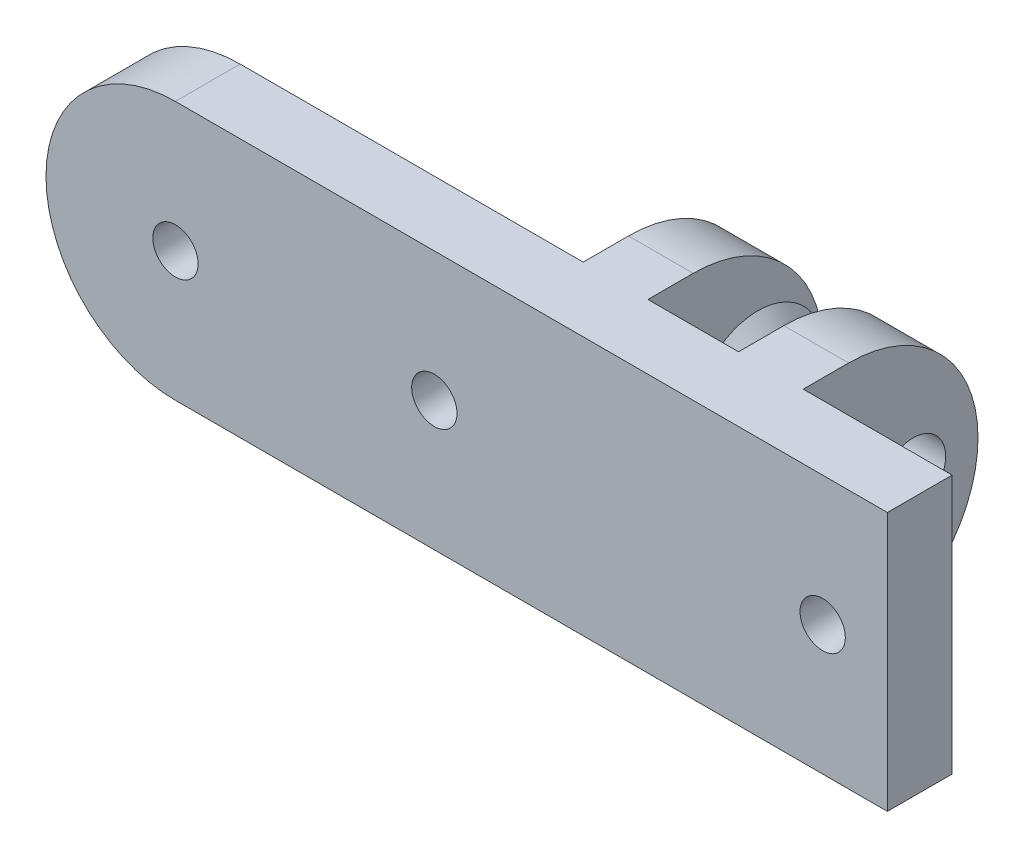
SolidWorks part; units mm, degrees
ref_plane "Спереди" through (0, 0, 0) normal (0, 0, 1) x (1, 0, 0)
ref_plane "Сверху" through (0, 0, 0) normal (0, 1, 0) x (1, 0, 0)
ref_plane "Справа" through (0, 0, 0) normal (1, 0, 0) x (0, 0, -1)
sketch "Эскиз1" plane through (0, 0, 0) normal (0, 0, 1) x (1, 0, 0)
  line L1 (-20, -10) -> (20, -10)
  line L2 (-20, -10) -> (-20, 10)
  line L3 (-20, 10) -> (20, 10)
  line L4 (20, -10) -> (20, 10)
  line L5 (-20, -10) -> (20, 10) construction
  line L6 (-20, 10) -> (20, -10) construction
  line L7 (-3.5, -10) -> (3.5, -10)
  line L8 (-3.5, -10) -> (-3.5, 10)
  line L9 (-3.5, 10) -> (3.5, 10)
  line L10 (3.5, -10) -> (3.5, 10)
  line L11 (-3.5, -10) -> (3.5, 10) construction
  line L12 (-3.5, 10) -> (3.5, -10) construction
  line L13 (-20, 10) -> (-45, 10)
  line L14 (-20, 10) -> (-20, -10)
  line L15 (-20, -10) -> (-45, -10)
  line L16 (-45, 10) -> (-45, -10)
  circle A0 centre (-15, 0) radius 1.75 construction
  circle A1 centre (15, 0) radius 1.75 construction
  circle A2 centre (-15, 0) radius 1.75
  circle A3 centre (15, 0) radius 1.75
  point P0 (0, 0)
  point P12 (0, 0)
  dimension "D1" = 40
  dimension "D2" = 20
  dimension "D3" = 7
  dimension "D4" = 25
extrude "Бобышка-Вытянуть1" add sketch "Эскиз1" along normal blind 5 contours L1 L8 L3 L2 A2 | L10 L1 L4 L3 A3 | L1 L10 L3 L8 | L13 L16 L15 L2 region at (-11.6524, 0, 0) region at (-32.5, 0, 0) region at (0, 0, 0) region at (11.6524, 0, 0)
sketch "Эскиз2" plane through (0, 0, 0) normal (0, 0, -1) x (-1, 0, 0)
  line L1 (8.5, 10) -> (3.5, 10)
  line L2 (8.5, 10) -> (8.5, -10)
  line L3 (8.5, -10) -> (3.5, -10)
  line L4 (3.5, 10) -> (3.5, -10)
  line L6 (0, 10) -> (0, -10) construction
  line L7 (-3.5, 10) -> (-3.5, -10)
  line L8 (-8.5, -10) -> (-3.5, -10)
  line L9 (-8.5, 10) -> (-8.5, -10)
  line L10 (-8.5, 10) -> (-3.5, 10)
  line L11 (45, 10) -> (-20, 10) construction
  line L12 (45, -10) -> (-20, -10) construction
  dimension "D1" = 5
  dimension "D2" = 7
extrude "Бобышка-Вытянуть2" add sketch "Эскиз2" along normal blind 13.5
sketch "Эскиз3" plane through (8.5, 0, 0) normal (1, 0, 0) x (0, 0, -1)
  line L0 (13.5, 10) -> (13.5, -10) construction
  circle A1 centre (8.5, 0) radius 2.5
  dimension "D1" = 5
  dimension "D3" = 5
extrude "Вырез-Вытянуть1" cut sketch "Эскиз3" against normal blind 25 contours A1 region at (8.5, 0, -8.5)
sketch "Эскиз4" plane through (3.5, 0, 0) normal (-1, 0, 0) x (0, 0, 1)
  circle A0 centre (-8.5, 0) radius 2.5 construction
  circle A1 centre (-8.5, 0) radius 2.5
  circle A2 centre (-8.5, 0) radius 4
  dimension "D1" = 1.5
extrude "Бобышка-Вытянуть3" add sketch "Эскиз4" along normal blind 1
ref_plane "Плоскость1" through (0, 0, 0) normal (1, 0, 0) x (0, 0, -1)
sketch "Эскиз5" plane through (-3.5, 0, 0) normal (1, 0, 0) x (0, 0, -1)
  circle A0 centre (8.5, 0) radius 2.5 construction
  circle A1 centre (8.5, 0) radius 4 construction
  circle A2 centre (8.5, 0) radius 2.5
  circle A3 centre (8.5, 0) radius 4
extrude "Бобышка-Вытянуть4" add sketch "Эскиз5" along normal blind 1
chamfer "Фаска1" distance 1 angle 45 1 edges at (-3.5, -4, -8.5)
chamfer "Фаска2" distance 1 angle 45 1 edges at (3.5, 4, -8.5)
fillet "Скругление1" radius 10 2 edges at (6, 10, -13.5) (6, -10, -13.5)
fillet "Скругление2" radius 10 2 edges at (-6, 10, -13.5) (-6, -10, -13.5)
sketch "Эскиз7" plane through (0, 0, 5) normal (0, 0, 1) x (1, 0, 0)
  line L0 (-45, 10) -> (20, 10) construction
  line L1 (-45, 10) -> (-45, -10) construction
  circle A0 centre (-35, 0) radius 10
  circle A1 centre (-35, 0) radius 1.75
  line M3 (-45, -10) -> (20, -10)
  line M5 (20, 10) -> (-45, 10)
  line M6 (-45, 10) -> (-45, -10)
  dimension "D1" = 3.5
extrude "Вырез-Вытянуть2" cut sketch "Эскиз7" against normal blind 5.5 contours A0 M5 M6 | A0 M6 M3 | A1 region at (-42.7663, 7.7663, 5) region at (-42.7663, -7.7663, 5)
